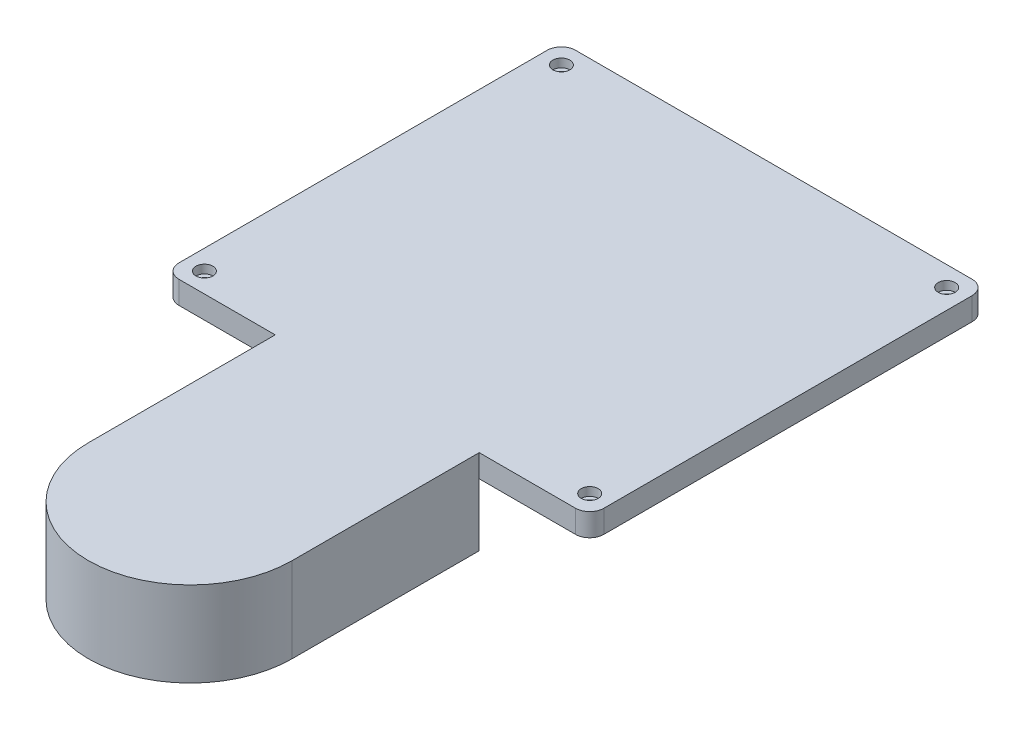
SolidWorks part; units mm, degrees
ref_plane "Front Plane" through (0, 0, 0) normal (0, 0, 1) x (1, 0, 0)
ref_plane "Top Plane" through (0, 0, 0) normal (0, 1, 0) x (1, 0, 0)
ref_plane "Right Plane" through (0, 0, 0) normal (1, 0, 0) x (0, 0, -1)
sketch "Sketch1" plane through (0, 0, 0) normal (0, 1, 0) x (1, 0, 0)
  line L0 (0, 0) -> (0, 50000) construction
  line L1 (36, 0) -> (36, 66)
  line L2 (-70, 206) -> (70, 206)
  line L3 (-75, 201) -> (-75, 71)
  line L4 (-70, 66) -> (70, 66)
  line L5 (75, 201) -> (75, 71)
  line L6 (-75, 206) -> (75, 66) construction
  line L7 (-75, 66) -> (75, 206) construction
  line L8 (-36, 0) -> (-36, 66)
  arc A0 (-36, 0) -> (36, 0) centre (0, 0) ccw
  arc A1 (-75, 71) -> (-70, 66) centre (-70, 71) ccw
  arc A2 (70, 66) -> (75, 71) centre (70, 71) ccw
  arc A3 (70, 206) -> (75, 201) centre (70, 201) cw
  arc A4 (-70, 206) -> (-75, 201) centre (-70, 201) ccw
  point P1 (0, -36)
  point P3 (0, 136)
  dimension "D1" = 72
  dimension "D5" = 5
  dimension "D2" = 150
  dimension "D3" = 140
  dimension "D4" = 102
extrude "Boss-Extrude1" add sketch "Sketch1" against normal blind 30 contours L8 A0 L1 L4 region at (0, 0, -18.5204)
shell "Shell1" thickness 3 removed face at (0, -15, -66)
extrude "Boss-Extrude2" add sketch "Sketch1<3>" against normal blind 8 contours L2 A4 L3 A1 L4 A2 L5 A3 region at (0, 0, -136)
sketch "Sketch1<3>" plane through (0, 0, 0) normal (0, 1, 0) x (1, 0, 0) same geometry as "Sketch1"
sketch "Sketch2" plane through (0, -30, 0) normal (0, -1, 0) x (1, 0, 0)
  circle A0 centre (13, -10.3) radius 8.5
  circle A1 centre (-13, -10.3) radius 8.5
  dimension "D1" = 17
  dimension "D2" = 17
extrude "Cut-Extrude1" cut sketch "Sketch2" against normal blind 6.5
sketch "Sketch5" plane through (0, -30, 0) normal (0, -1, 0) x (1, 0, 0)
  circle A0 centre (0, 8) radius 6
  dimension "D1" = 12
extrude "Cut-Extrude4" cut sketch "Sketch5" against normal blind 13
sketch "Sketch6" plane through (0, -30, 0) normal (0, -1, 0) x (1, 0, 0)
  circle A0 centre (0, 8) radius 6
  circle A1 centre (0, 8) radius 9
  dimension "D2" = 12
  dimension "D1" = 3
extrude "Boss-Extrude3" add sketch "Sketch6" along normal blind 5
sketch "Sketch7" plane through (0, -30, 0) normal (0, -1, 0) x (1, 0, 0)
  circle A0 centre (0, 24) radius 4
  circle A1 centre (0, 24) radius 6
  arc A2 (36, 0) -> (-36, 0) centre (0, 0) ccw construction
  point P7 (0, 36)
  dimension "D1" = 8
  dimension "D3" = 12
  dimension "D2" = 2
extrude "Cut-Extrude5" cut sketch "Sketch7" against normal blind 7 contours A0 region at (0, -30, 24)
extrude "Boss-Extrude4" add sketch "Sketch7<3>" along normal blind 5
sketch "Sketch7<3>" plane through (0, -30, 0) normal (0, -1, 0) x (1, 0, 0) same geometry as "Sketch7"
sketch "Sketch8" plane through (0, -8, 0) normal (0, -1, 0) x (1, 0, 0)
  circle A0 centre (68, -73) radius 1.5
  circle A1 centre (68, -199) radius 1.5
  circle A2 centre (-68, -199) radius 1.5
  circle A3 centre (-68, -73) radius 1.5
extrude "Cut-Extrude6" cut sketch "Sketch8" against normal through all
sketch "Sketch9" plane through (0, 0, 0) normal (0, 1, 0) x (1, 0, 0)
  circle A0 centre (-68, 73) radius 3
  circle A1 centre (-68, 199) radius 3
  circle A2 centre (68, 199) radius 3
  circle A3 centre (68, 73) radius 3
  dimension "D1" = 6
  dimension "D2" = 6
  dimension "D3" = 6
  dimension "D4" = 6
extrude "Cut-Extrude7" cut sketch "Sketch9" against normal blind 3
